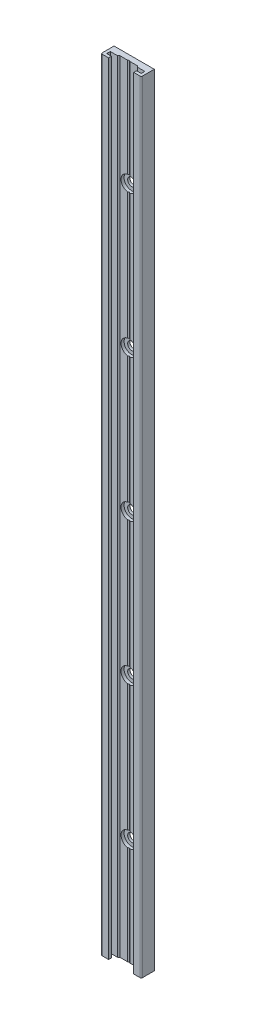
SolidWorks part; units mm, degrees
ref_plane "Front Plane" through (0, 0, 0) normal (0, 0, 1) x (1, 0, 0)
ref_plane "Top Plane" through (0, 0, 0) normal (0, 1, 0) x (1, 0, 0)
ref_plane "Right Plane" through (0, 0, 0) normal (1, 0, 0) x (0, 0, -1)
ref_plane "Plane1" through (0, 165, 0) normal (0, 1, 0) x (1, 0, 0)
sketch "Sketch1" plane through (0, 165, 0) normal (0, 1, 0) x (1, 0, 0)
  line L0 (-8, -5.5) -> (8, -5.5)
  line L1 (8.5, -5) -> (8.5, 0)
  line L2 (8.5, 0) -> (-8.5, 0)
  line L3 (-8.5, 0) -> (-8.5, -5)
  arc A0 (8, -5.5) -> (8.5, -5) centre (8, -5) ccw
  arc A1 (-8.5, -5) -> (-8, -5.5) centre (-8, -5) ccw
extrude "Boss-Extrude1" add sketch "Sketch1" against normal blind 330
sketch "Sketch2" plane through (0, -165, 0) normal (0, -1, 0) x (1, 0, 0)
  line L0 (5.3, 5.5) -> (-5.3, 5.5)
  line L1 (-5.3, 5.5) -> (-5.3, 4.3)
  line L2 (-5.3, 4.3) -> (-7.3, 4.3)
  line L3 (-7.3, 4.3) -> (-7.3, 2.8)
  line L4 (-7.3, 2.8) -> (-4.25, 2.8)
  line L5 (-4.25, 2.8) -> (-3.75, 2.3)
  line L6 (-3.75, 2.3) -> (-0.5, 2.3)
  line L7 (-0.5, 2.3) -> (0, 2.0113)
  line L8 (0, 2.0113) -> (0.5, 2.3)
  line L9 (0.5, 2.3) -> (3.75, 2.3)
  line L10 (3.75, 2.3) -> (4.25, 2.8)
  line L11 (4.25, 2.8) -> (7.3, 2.8)
  line L12 (7.3, 2.8) -> (7.3, 4.3)
  line L13 (7.3, 4.3) -> (5.3, 4.3)
  line L14 (5.3, 4.3) -> (5.3, 5.5)
extrude "Cut-Extrude1" cut sketch "Sketch2" against normal through all
ref_plane "Plane2" through (0, 120, 0) normal (0, 1, 0) x (1, 0, 0)
sketch "Sketch3" plane through (0, 120, 0) normal (0, 1, 0) x (1, 0, 0)
  line L0 (1.75, 0) -> (0, 0)
  line L1 (0, 0) -> (0, -2.3)
  line L2 (0, -2.3) -> (3.25, -2.3)
  line L3 (3.25, -2.3) -> (3.25, -1)
  line L4 (3.25, -1) -> (1.75, -1)
  line L5 (1.75, -1) -> (1.75, 0)
  line L6 (0, 0) -> (0, -2.3) construction
revolve "Cut-Revolve1" cut sketch "Sketch3" angle 360 about L6 reverse direction yes
sketch3d "3DSketch1"
  point P0 (0, -0.346, 1.9407)
  point P1 (0, -100.346, 1.9407)
ref_axis "Axis1" through (0, -0.346, 1.9407) along (0, -1, 0)
pattern_linear "LPattern1" count 5 spacing 60 along (0, -1, 0) of "Cut-Revolve1"
ref_plane "Plane3" through (0, 0, 0) normal (1, 0, 0) x (0, 0, -1)
ref_plane "Plane4" through (0, 0, 0) normal (0, -1, 0) x (-1, 0, 0)
